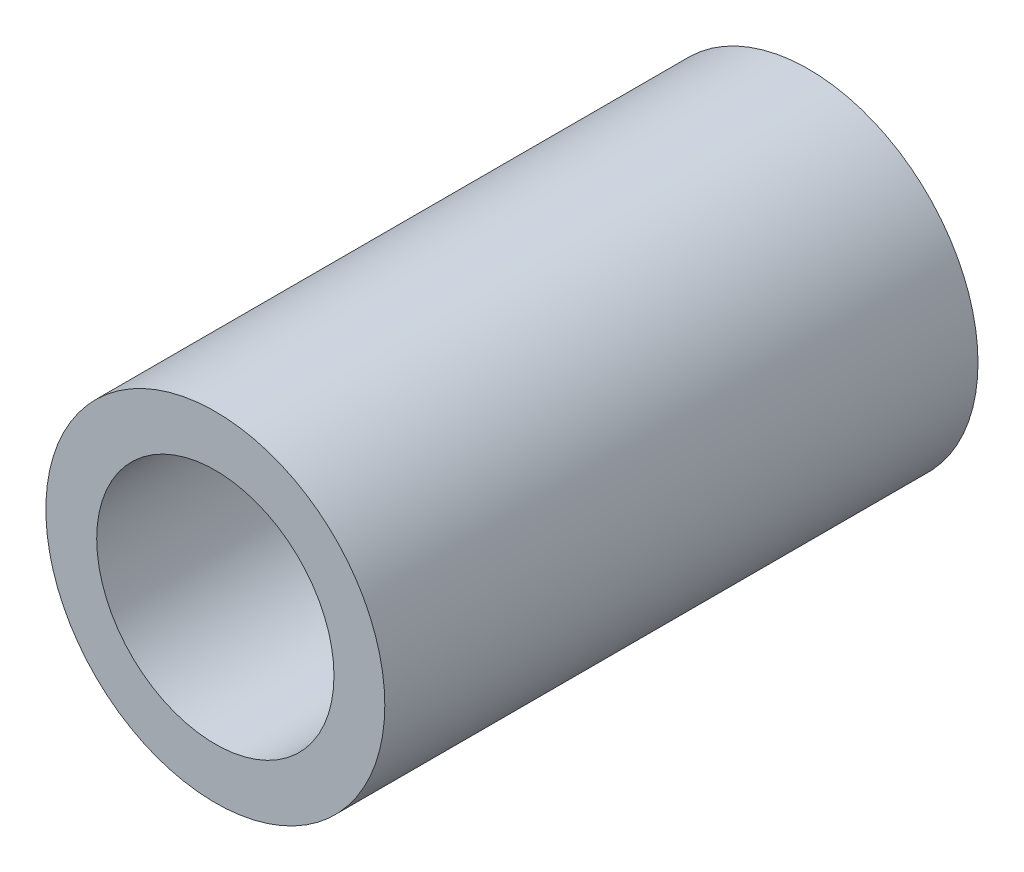
SolidWorks part; units mm, degrees
ref_plane "Front Plane" through (0, 0, 0) normal (0, 0, 1) x (1, 0, 0)
ref_plane "Top Plane" through (0, 0, 0) normal (0, 1, 0) x (1, 0, 0)
ref_plane "Right Plane" through (0, 0, 0) normal (1, 0, 0) x (0, 0, -1)
sketch "Sketch1" plane through (0, 0, 0) normal (0, 0, 1) x (1, 0, 0)
  circle A0 centre (0, 0) radius 6.35
  circle A1 centre (0, 0) radius 4.445
  dimension "D1" = 8.89
  dimension "D2" = 12.7
extrude "Boss-Extrude1" add sketch "Sketch1" along normal mid plane 22.225
